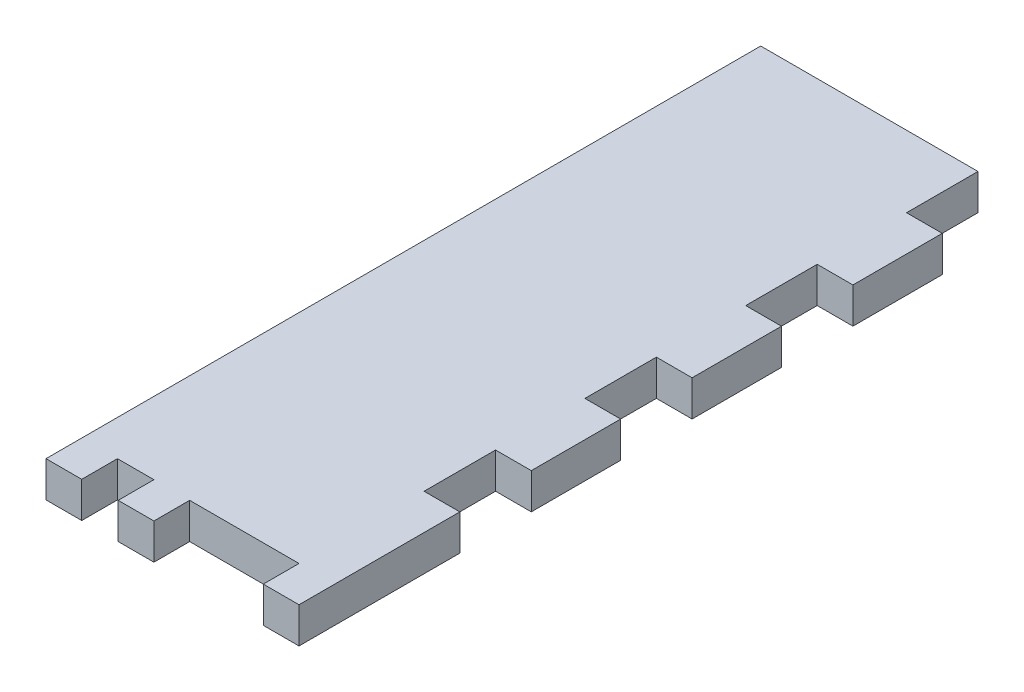
SolidWorks part; units mm, degrees
material "Acrylic (Medium-high impact)"
ref_plane "Front" through (0, 0, 0) normal (0, 0, 1) x (1, 0, 0)
ref_plane "Top" through (0, 0, 0) normal (0, 1, 0) x (1, 0, 0)
ref_plane "Right" through (0, 0, 0) normal (1, 0, 0) x (0, 0, -1)
sketch "Sketch1" plane through (0, 0, 0) normal (0, 0, 1) x (1, 0, 0)
  line L0 (0, 143.002) -> (0, -143.002) construction
  line L1 (-3.302, 133.858) -> (-3.302, -143.002)
  line L2 (-3.302, -143.002) -> (3.302, -143.002)
  line L3 (3.302, 143.002) -> (3.302, -143.002)
  line L4 (3.302, 143.002) -> (-16.256, 143.002)
  line L5 (-5.842, 136.398) -> (-16.256, 136.398)
  line L6 (-16.256, 143.002) -> (-16.256, 136.398)
  line L8 (-28.956, 155.448) -> (16.002, 155.448)
  line L9 (-28.956, 155.448) -> (-28.956, -149.352)
  line L10 (-28.956, -149.352) -> (16.002, -149.352)
  line L11 (16.002, 155.448) -> (16.002, -149.352)
  arc A0 (-3.302, 133.858) -> (-5.842, 136.398) centre (-5.842, 133.858) ccw
  point P2 (0, -143.002)
  point P11 (0, 0)
  dimension "D5" = 2.54
  dimension "D1" = 6.604
  dimension "D2" = 12.954
  dimension "D3" = 6.604
  dimension "D4" = 286.004
  dimension "D6" = 304.8
  dimension "D7" = 6.35
  dimension "D8" = 12.7
  dimension "D9" = 12.7
extrude "Boss-Extrude1" add sketch "Sketch1" along normal blind 6.35
sketch "Sketch2" plane through (16.002, 0, 0) normal (1, 0, 0) x (0, 0, -1)
  line L0 (-6.35, -149.352) -> (-6.35, 155.448) construction
  line L1 (-6.35, -47.752) -> (127, -47.752)
  line L2 (-6.35, -47.752) -> (-6.35, -149.352)
  line L3 (-6.35, -149.352) -> (127, -149.352)
  line L4 (127, -47.752) -> (127, -149.352)
  line L5 (14.4, -101.092) -> (14.4, -96.012)
  line L6 (36.4, -96.012) -> (36.4, -101.092)
  line L7 (8.4, -116.592) -> (8.4, -111.512)
  line L8 (11.4, -116.592) -> (11.4, -111.512)
  line L9 (8.4, -85.592) -> (8.4, -80.512)
  line L10 (11.4, -85.592) -> (11.4, -80.512)
  line L11 (25.4, -96.012) -> (25.4, -101.092) construction
  line L12 (42.4, -116.592) -> (42.4, -111.512)
  line L13 (39.4, -116.592) -> (39.4, -111.512)
  line L14 (39.4, -85.592) -> (39.4, -80.512)
  line L15 (42.4, -85.592) -> (42.4, -80.512)
  line L16 (0, -149.352) -> (0, 155.448) construction
  line L17 (123.825, -60.452) -> (123.825, -77.3853) construction
  line L18 (127, -47.752) -> (120.65, -47.752)
  line L19 (127, -47.752) -> (127, -60.452)
  line L20 (127, -60.452) -> (120.65, -60.452)
  line L21 (120.65, -47.752) -> (120.65, -60.452)
  line L22 (127, -107.0187) -> (120.65, -107.0187)
  line L23 (127, -107.0187) -> (127, -119.7187)
  line L24 (127, -119.7187) -> (120.65, -119.7187)
  line L25 (120.65, -107.0187) -> (120.65, -119.7187)
  line L26 (127, -136.652) -> (120.65, -136.652)
  line L27 (127, -136.652) -> (127, -149.352)
  line L28 (127, -149.352) -> (120.65, -149.352)
  line L29 (120.65, -136.652) -> (120.65, -149.352)
  line L30 (127, -77.3853) -> (120.65, -77.3853)
  line L31 (127, -77.3853) -> (127, -90.0853)
  line L32 (127, -90.0853) -> (120.65, -90.0853)
  line L33 (120.65, -77.3853) -> (120.65, -90.0853)
  line L34 (123.825, -90.0853) -> (123.825, -107.0187) construction
  line L35 (123.825, -119.7187) -> (123.825, -136.652) construction
  arc A0 (14.4, -101.092) -> (36.4, -101.092) centre (25.4, -101.092) ccw
  arc A1 (36.4, -96.012) -> (14.4, -96.012) centre (25.4, -96.012) ccw
  arc A2 (8.4, -116.592) -> (11.4, -116.592) centre (9.9, -116.592) ccw
  arc A3 (11.4, -111.512) -> (8.4, -111.512) centre (9.9, -111.512) ccw
  arc A4 (8.4, -85.592) -> (11.4, -85.592) centre (9.9, -85.592) ccw
  arc A5 (11.4, -80.512) -> (8.4, -80.512) centre (9.9, -80.512) ccw
  arc A6 (42.4, -116.592) -> (39.4, -116.592) centre (40.9, -116.592) cw
  arc A7 (39.4, -111.512) -> (42.4, -111.512) centre (40.9, -111.512) cw
  arc A8 (42.4, -85.592) -> (39.4, -85.592) centre (40.9, -85.592) cw
  arc A9 (39.4, -80.512) -> (42.4, -80.512) centre (40.9, -80.512) cw
  point P44 (25.4, -98.552)
  point P47 (-6.35, -98.552)
  line M17 (0, -149.352) -> (0, 155.448)
  line M19 (-6.35, 155.448) -> (-6.35, -149.352)
  line M20 (-6.35, -149.352) -> (0, -149.352)
  dimension "D1" = 22
  dimension "D6" = 1.5
  dimension "D10" = 1.5
  dimension "D2" = 5.08
  dimension "D3" = 5.08
  dimension "D4" = 15.5
  dimension "D5" = 15.5
  dimension "D7" = 15.5
  dimension "D8" = 15.5
  dimension "D9" = 5.08
  dimension "D11" = 25.4
  dimension "D12" = 50.8
  dimension "D13" = 101.6
  dimension "D14" = 12.7
  dimension "D15" = 6.35
extrude "Boss-Extrude2" add sketch "Sketch2" against normal blind 6.35 contours L33 L30 L4 L20 L21 L1 L3 L29 L26 L24 L25 L22 L32 A5 L10 A4 L9 A3 L8 A2 L7 A1 L6 A0 L5 L13 A7 L12 A6 L14 A9 L15 A8 M17 | L1 M19 M20 M17 region at (16.002, -98.552, -63.7235) region at (16.002, -98.552, 3.175)
sketch "Sketch3" plane through (9.652, 0, 0) normal (-1, 0, 0) x (0, 0, 1)
  line L0 (-120.65, -136.652) -> (-120.65, -149.352) construction
  line L1 (-120.65, -143.002) -> (0, -143.002)
  line L2 (-120.65, -143.002) -> (-120.65, -149.352)
  line L3 (-120.65, -149.352) -> (0, -149.352)
  line L4 (0, -143.002) -> (0, -149.352)
  dimension "D1" = 6.35
extrude "Boss-Extrude3" add sketch "Sketch3" along normal up to surface (38.608 mm away) up to face at (-28.956, 3.048, 3.175)
sketch "Sketch4" plane through (0, -149.352, 0) normal (0, -1, 0) x (1, 0, 0)
  line L0 (9.652, -22.225) -> (9.652, -34.925)
  line L1 (16.002, 6.35) -> (9.652, 6.35)
  line L2 (16.002, 6.35) -> (16.002, -6.35)
  line L3 (16.002, -6.35) -> (9.652, -6.35)
  line L4 (9.652, 6.35) -> (9.652, -6.35)
  line L5 (16.002, -22.225) -> (9.652, -22.225)
  line L6 (16.002, -22.225) -> (16.002, -34.925)
  line L7 (16.002, -34.925) -> (9.652, -34.925)
  line L8 (9.652, -50.8) -> (9.652, -63.5)
  line L9 (16.002, -50.8) -> (9.652, -50.8)
  line L10 (16.002, -50.8) -> (16.002, -63.5)
  line L11 (16.002, -63.5) -> (9.652, -63.5)
  line L12 (9.652, -79.375) -> (9.652, -92.075)
  line L13 (16.002, -79.375) -> (9.652, -79.375)
  line L14 (16.002, -79.375) -> (16.002, -92.075)
  line L15 (16.002, -92.075) -> (9.652, -92.075)
  line L36 (-6.477, 6.35) -> (-6.477, -120.65) construction
  line L37 (-28.956, 6.35) -> (16.002, 6.35) construction
  line L38 (-28.956, -120.65) -> (16.002, -120.65) construction
  line L39 (-22.606, 6.35) -> (-22.606, -120.65)
  line L40 (16.002, 6.35) -> (9.652, 6.35)
  line L41 (16.002, 6.35) -> (16.002, -120.65)
  line L42 (16.002, -120.65) -> (9.652, -120.65)
  line L43 (9.652, 6.35) -> (9.652, -120.65)
  line L44 (-28.956, -120.65) -> (-22.606, -120.65)
  line L45 (-28.956, 6.35) -> (-28.956, -120.65)
  line L46 (-28.956, 6.35) -> (-22.606, 6.35)
  line L47 (-28.956, -120.65) -> (-22.606, -120.65)
  line L48 (-28.956, -107.95) -> (-28.956, -120.65)
  line L49 (-28.956, -107.95) -> (-22.606, -107.95)
  line L50 (-22.606, -107.95) -> (-22.606, -120.65)
  line L51 (-28.956, -106.3625) -> (-22.606, -106.3625)
  line L52 (-28.956, -93.6625) -> (-28.956, -106.3625)
  line L53 (-28.956, -93.6625) -> (-22.606, -93.6625)
  line L54 (-22.606, -93.6625) -> (-22.606, -106.3625)
  line L55 (-28.956, -92.075) -> (-22.606, -92.075)
  line L56 (-28.956, -79.375) -> (-28.956, -92.075)
  line L57 (-28.956, -79.375) -> (-22.606, -79.375)
  line L58 (-22.606, -79.375) -> (-22.606, -92.075)
  line L59 (-28.956, -77.7875) -> (-22.606, -77.7875)
  line L60 (-28.956, -65.0875) -> (-28.956, -77.7875)
  line L61 (-28.956, -65.0875) -> (-22.606, -65.0875)
  line L62 (-22.606, -65.0875) -> (-22.606, -77.7875)
  line L63 (-28.956, -63.5) -> (-22.606, -63.5)
  line L64 (-28.956, -50.8) -> (-28.956, -63.5)
  line L65 (-28.956, -50.8) -> (-22.606, -50.8)
  line L66 (-22.606, -50.8) -> (-22.606, -63.5)
  line L67 (-28.956, -92.075) -> (-22.606, -92.075)
  line L68 (-28.956, -79.375) -> (-28.956, -92.075)
  line L69 (-28.956, -79.375) -> (-22.606, -79.375)
  line L70 (-22.606, -79.375) -> (-22.606, -92.075)
  line L71 (-28.956, -63.5) -> (-22.606, -63.5)
  line L72 (-28.956, -50.8) -> (-28.956, -63.5)
  line L73 (-28.956, -50.8) -> (-22.606, -50.8)
  line L74 (-22.606, -50.8) -> (-22.606, -63.5)
  line L75 (-28.956, -34.925) -> (-22.606, -34.925)
  line L76 (-28.956, -22.225) -> (-28.956, -34.925)
  line L77 (-28.956, -22.225) -> (-22.606, -22.225)
  line L78 (-22.606, 6.35) -> (-22.606, -6.35)
  line L79 (-28.956, -6.35) -> (-22.606, -6.35)
  line L80 (-28.956, 6.35) -> (-28.956, -6.35)
  line L81 (-28.956, 6.35) -> (-22.606, 6.35)
  line L82 (-22.606, -22.225) -> (-22.606, -34.925)
  line L83 (-16.129, 3.175) -> (-22.606, 3.175) construction
  line L85 (-28.956, 6.35) -> (-22.606, 6.35)
  line L86 (-28.956, 6.35) -> (-28.956, 0)
  line L87 (-28.956, 0) -> (-22.606, 0)
  line L88 (-22.606, 6.35) -> (-22.606, 0)
  line L92 (9.652, 6.35) -> (9.652, 0)
  line L93 (9.652, 6.35) -> (16.002, 6.35)
  line L94 (16.002, 6.35) -> (16.002, 0)
  line L95 (9.652, 0) -> (16.002, 0)
  line L100 (-9.652, 6.35) -> (-9.652, 0) [skipped]
  line L101 (-9.652, 0) -> (-3.302, 0) [skipped]
  line L102 (-3.302, 6.35) -> (-3.302, 0) [skipped]
  line L103 (-9.652, 6.35) -> (-3.302, 6.35) [skipped]
  line L104 (-9.779, 0) -> (-16.129, 0)
  line L105 (-9.779, 0) -> (-9.779, 6.35)
  line L106 (-9.779, 6.35) -> (-16.129, 6.35)
  line L107 (-16.129, 0) -> (-16.129, 6.35)
  line L108 (-9.779, 3.175) -> (-3.302, 3.175) construction
  line L109 (-3.302, 6.35) -> (-3.302, 0) construction
  line L110 (-22.606, 6.35) -> (-16.129, 6.35)
  line L115 (-28.956, 6.35) -> (16.002, 6.35)
  line L116 (-28.956, 6.35) -> (-28.956, 0)
  line L117 (-28.956, 0) -> (16.002, 0)
  line L118 (16.002, 6.35) -> (16.002, 0)
  line L119 (-28.956, 6.35) -> (16.002, 6.35)
  line L120 (-28.956, 6.35) -> (-28.956, 0)
  line L121 (-28.956, 0) -> (16.002, 0)
  line L122 (16.002, 6.35) -> (16.002, 0)
  line L123 (-22.606, 0) -> (-16.129, 0)
  line L124 (-9.779, 6.35) -> (9.652, 6.35)
  line L125 (-9.779, 0) -> (9.652, 0)
  line L126 (9.652, -107.95) -> (9.652, -120.65)
  line L127 (16.002, -107.95) -> (9.652, -107.95)
  line L128 (16.002, -107.95) -> (16.002, -120.65)
  line L129 (16.002, -120.65) -> (9.652, -120.65)
  line M38 (16.002, -120.65) -> (16.002, 6.35)
  line M41 (-28.956, -120.65) -> (16.002, -120.65)
  dimension "D1" = 6.35
  dimension "D2" = 12.7
  dimension "D4" = 6.35
  dimension "D5" = 6.35
  dimension "D7" = 6.35
  dimension "D3" = 5
  dimension "D6" = 3
sketch "Sketch6" plane through (0, 0, 6.35) normal (0, 0, 1) x (1, 0, 0)
  line L1 (16.002, -60.452) -> (9.652, -60.452)
  line L2 (16.002, -60.452) -> (16.002, -77.3853)
  line L3 (16.002, -77.3853) -> (9.652, -77.3853)
  line L4 (9.652, -60.452) -> (9.652, -77.3853)
  line L5 (16.002, -90.0853) -> (9.652, -90.0853)
  line L6 (16.002, -90.0853) -> (16.002, -107.0187)
  line L7 (16.002, -107.0187) -> (9.652, -107.0187)
  line L8 (9.652, -90.0853) -> (9.652, -107.0187)
  line L9 (16.002, -119.7187) -> (9.652, -119.7187)
  line L10 (16.002, -119.7187) -> (16.002, -136.652)
  line L11 (16.002, -136.652) -> (9.652, -136.652)
  line L12 (9.652, -119.7187) -> (9.652, -136.652)
sketch "Sketch7" plane through (16.002, 0, 0) normal (1, 0, 0) x (0, 0, -1)
  line L1 (-6.35, 180.723) -> (327.0227, 180.723)
  line L2 (-6.35, 180.723) -> (-6.35, -143.002)
  line L3 (-6.35, -143.002) -> (327.0227, -143.002)
  line L4 (327.0227, 180.723) -> (327.0227, -143.002)
  line L5 (-6.35, -149.352) -> (-6.35, 155.448) construction
  line L6 (120.65, -143.002) -> (0, -143.002) construction
  point P10 (160.3364, -143.002)
extrude "Cut-Extrude1" cut sketch "Sketch7" against normal through all
extrude "Cut-Extrude2" cut sketch "Sketch4" against normal blind 6.35 contours L7 L5 L0 M38 | L11 L9 L8 M38 | L15 L13 L12 M38 | L127 L43 M38 M41 region at (12.827, -149.352, -28.575) region at (12.827, -149.352, -57.15) region at (12.827, -149.352, -85.725) region at (12.827, -149.352, -114.3)
sketch "Sketch8" plane through (0, -149.352, 0) normal (0, -1, 0) x (1, 0, 0)
  line L1 (-22.606, 6.35) -> (-16.129, 6.35)
  line L2 (-22.606, 6.35) -> (-22.606, 0)
  line L3 (-22.606, 0) -> (-16.129, 0)
  line L4 (-16.129, 6.35) -> (-16.129, 0)
  line L5 (-9.779, 6.35) -> (9.652, 6.35)
  line L6 (-9.779, 6.35) -> (-9.779, 0)
  line L7 (-9.779, 0) -> (9.652, 0)
  line L8 (9.652, 6.35) -> (9.652, 0)
extrude "Cut-Extrude4" cut sketch "Sketch8" against normal through all
